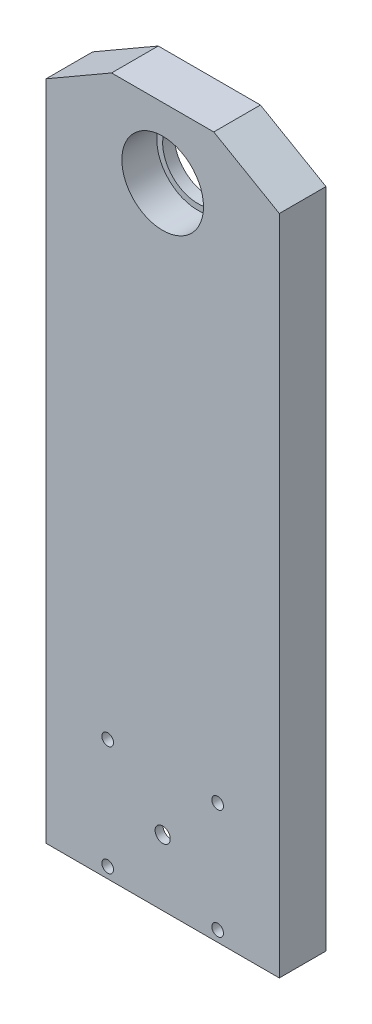
SolidWorks part; units mm, degrees
material "3.1325 (EN-AW 2017A)"
ref_plane "Płaszczyzna przednia" through (0, 0, 0) normal (0, 0, 1) x (1, 0, 0)
ref_plane "Płaszczyzna górna" through (0, 0, 0) normal (0, 1, 0) x (1, 0, 0)
ref_plane "Płaszczyzna prawa" through (0, 0, 0) normal (1, 0, 0) x (0, 0, -1)
other "Środek masy(COM)"
sketch "Szkic1" plane through (0, 0, 0) normal (0, 0, 1) x (1, 0, 0)
  line L0 (0, 0) -> (0, 300) construction
  line L1 (50, 0) -> (-50, 0)
  line L2 (-50, 0) -> (-50, 283.7766)
  line L3 (-21.9003, 300) -> (21.9003, 300)
  line L4 (-21.9003, 300) -> (-50, 283.7766)
  line L5 (21.9003, 300) -> (50, 283.7766)
  line L6 (50, 0) -> (50, 283.7766)
  line L7 (21.9003, 270) -> (-21.9003, 270) construction
  circle A0 centre (0, 270) radius 15
  circle A1 centre (0, 270) radius 17.5
  dimension "D3" = 300
  dimension "D5" = 30
  dimension "D6" = 35
  dimension "D1" = 30
  dimension "D2" = 50
  dimension "D4" = 30
extrude "Dodanie-wyciągnięcie1" add sketch "Szkic1" along normal blind 20 contours L1 L0 A1 L3 L4 L2 | L0 L1 L6 L5 L3 A1 region at (0, 143.6544, 0)
extrude "Dodanie-wyciągnięcie2" add sketch "Szkic1<3>" along normal blind 5 contours A1 L0 A0 | L0 A1 A0 region at (-17.005, 270, 0)
sketch "Szkic1<3>" plane through (0, 0, 0) normal (0, 0, 1) x (1, 0, 0) same geometry as "Szkic1"
sketch "Szkic2" plane through (0, 0, 0) normal (0, -1, 0) x (-1, 0, 0)
  line L0 (0, 0) -> (0, -20) construction
  line L1 (-50, -20) -> (50, -20) construction
  line L2 (-50, -10) -> (50, -10) construction
  line L3 (-50, -20) -> (-50, 0) construction
  line L4 (50, -20) -> (50, 0) construction
  point P11 (35, -10)
  point P12 (-35, -10)
  dimension "D1" = 70
hole_wizard "Otwór gwintowany M81" positions "Szkic 3D1" profile "Szkic3" tap size "M8" standard "ISO"
sketch3d "Szkic 3D1"
  point P0 (-35, 0, 10)
  point P3 (35, 0, 10)
sketch "Szkic3" plane through (-35, 0, 10) normal (1, 0, 0) x (0, 0, -1)
  line L0 (0, 0) -> (0, 28.2929)
  line L1 (0, 28.2929) -> (3.4, 26.25)
  line L2 (3.4, 26.25) -> (3.4, 0)
  line L5 (3.4, 0) -> (0, 0)
  line L10 (0, 28.2929) -> (-3.4, 26.25) construction
  line L11 (0, -6.35) -> (0, 107.95) construction
  dimension "Średnica wiertła gwintu" = 6.8
  dimension "Głębokość otworu gwintowanego" = 26.25
  dimension "Kąt wiertła" = 118
cosmetic thread "Gwint otworu1" parameters "D1"=20, "D2"=8
cosmetic thread "Gwint otworu2" parameters "D1"=20, "D2"=8
sketch "Szkic4" plane through (0, 0, 0) normal (0, 0, -1) x (-1, 0, 0)
  line L0 (50, 0) -> (50, 283.7766) construction
  line L1 (-28.2, 0) -> (28.2, 0)
  line L2 (-50, 0) -> (50, 0) construction
  line L3 (-28.2, 0) -> (-28.2, 53.4)
  line L4 (-25.2, 56.4) -> (25.2, 56.4)
  line L5 (28.2, 0) -> (28.2, 53.4)
  line L7 (-50, 0) -> (50, 0) construction
  arc A2 (28.2, 53.4) -> (25.2, 56.4) centre (25.2, 53.4) ccw
  arc A3 (-25.2, 56.4) -> (-28.2, 53.4) centre (-25.2, 53.4) ccw
  circle A4 centre (0, 28.2) radius 19.05
  circle A5 centre (0, 28.2) radius 3.25
  point P9 (0, 56.4)
  point P12 (-28.2, 0)
  point P15 (28.2, 0)
  point P18 (28.2, 56.4)
  point P21 (-28.2, 56.4)
  line M1 (-50, 0) -> (50, 0)
  dimension "D1" = 28.2
  dimension "D2" = 56.4
  dimension "D3" = 38.1
  dimension "D4" = 6.5
  dimension "D5" = 56.4
  dimension "D6" = 3
  dimension "D7" = 78.2
extrude "Wytnij-wyciągnięcie2" cut sketch "Szkic4" against normal blind 15 contours L4 A3 L3 L5 A2 A4 M1 | A4 A5 region at (27.4024, 26.7, 0) region at (18.5112, 28.2, 0)
extrude "Wytnij-wyciągnięcie3" cut sketch "Szkic4<4>" against normal blind 16.6 contours A4 A5 region at (18.5112, 28.2, 0)
sketch "Szkic4<4>" plane through (0, 0, 0) normal (0, 0, -1) x (-1, 0, 0) same geometry as "Szkic4"
extrude "Wytnij-wyciągnięcie4" cut sketch "Szkic4<5>" against normal blind 49.6 contours A5 region at (0, 28.2, 0)
sketch "Szkic4<5>" plane through (0, 0, 0) normal (0, 0, -1) x (-1, 0, 0) same geometry as "Szkic4"
sketch "Szkic5" plane through (0, 0, 15) normal (0, 0, -1) x (-1, 0, 0)
  line L0 (0, 28.2) -> (0, 56.4) construction
  line L1 (-25.2, 56.4) -> (25.2, 56.4) construction
  line L2 (0, 28.2) -> (-28.2, 28.2) construction
  line L3 (-28.2, 0) -> (-28.2, 53.4) construction
  circle A0 centre (-23.57, 51.77) radius 2.5
  circle A1 centre (23.57, 51.77) radius 2.5
  circle A2 centre (23.57, 4.63) radius 2.5
  circle A3 centre (-23.57, 4.63) radius 2.5
  dimension "D1" = 47.14
  dimension "D2" = 47.14
  dimension "D3" = 5
extrude "Wytnij-wyciągnięcie5" cut sketch "Szkic5" against normal blind 7.6
sketch "Szkic6" plane through (0, 0, 0) normal (0, 0, -1) x (-1, 0, 0)
  line L0 (0, 255) -> (0, 56.4) construction
  line L4 (-45, 228.9281) -> (-45, 82.4719)
  line L5 (2.2326, 145.7142) -> (38.3428, 74.0554)
  line L6 (45, 228.9281) -> (45, 82.4719)
  line L7 (-45, 245) -> (45, 66.4) construction
  line L8 (45, 245) -> (1.3997, 158.4777) construction
  line L9 (-40.0085, 240.65) -> (-2.2326, 165.6858)
  line L10 (-40.2674, 230.0531) -> (-5.0672, 160.2001)
  line L11 (40.0085, 240.65) -> (2.2326, 165.6858)
  line L12 (40.2674, 230.0531) -> (5.0672, 160.2001)
  line L13 (-35.6638, 69.7054) -> (35.6638, 69.7054)
  line L14 (-2.2326, 145.7142) -> (-38.3428, 74.0554)
  line L15 (-5.0672, 151.1999) -> (-40.2674, 81.3469)
  line L16 (0, 155.7) -> (-45, 66.4) construction
  line L17 (5.0672, 151.1999) -> (40.2674, 81.3469)
  line L18 (-37.3294, 245) -> (37.3294, 245)
  line L20 (-40.2674, 155.7) -> (38.3428, 155.7) construction
  line L21 (50, 0) -> (50, 283.7766) construction
  line L22 (28.2, 0) -> (50, 0) construction
  arc A1 (-40.2674, 230.0531) -> (-45, 228.9281) centre (-42.5, 228.9281) ccw
  arc A2 (-45, 82.4719) -> (-40.2674, 81.3469) centre (-42.5, 82.4719) ccw
  arc A3 (45, 82.4719) -> (40.2674, 81.3469) centre (42.5, 82.4719) cw
  arc A4 (-38.3428, 74.0554) -> (-35.6638, 69.7054) centre (-35.6638, 72.7054) ccw
  arc A5 (35.6638, 69.7054) -> (38.3428, 74.0554) centre (35.6638, 72.7054) ccw
  arc A6 (-37.3294, 245) -> (-40.0085, 240.65) centre (-37.3294, 242) ccw
  arc A7 (37.3294, 245) -> (40.0085, 240.65) centre (37.3294, 242) cw
  arc A8 (2.2326, 145.7142) -> (-2.2326, 145.7142) centre (0, 144.5892) ccw
  arc A9 (45, 228.9281) -> (40.2674, 230.0531) centre (42.5, 228.9281) ccw
  arc A10 (-5.0672, 151.1999) -> (-5.0672, 160.2001) centre (-13.9974, 155.7) ccw
  arc A11 (2.2326, 165.6858) -> (-2.2326, 165.6858) centre (0, 166.8108) cw
  arc A12 (5.0672, 151.1999) -> (5.0672, 160.2001) centre (13.9974, 155.7) cw
  dimension "D1" = 2.5
  dimension "D2" = 3
  dimension "D5" = 5
  dimension "D6" = 2.2326
  dimension "D3" = 10
  dimension "D4" = 95
  dimension "D7" = 0.259
  dimension "D8" = 1.6656
  dimension "D9" = 21.6663
  dimension "D10" = 66.4
extrude "Wytnij-wyciągnięcie6" cut sketch "Szkic6" against normal blind 10
